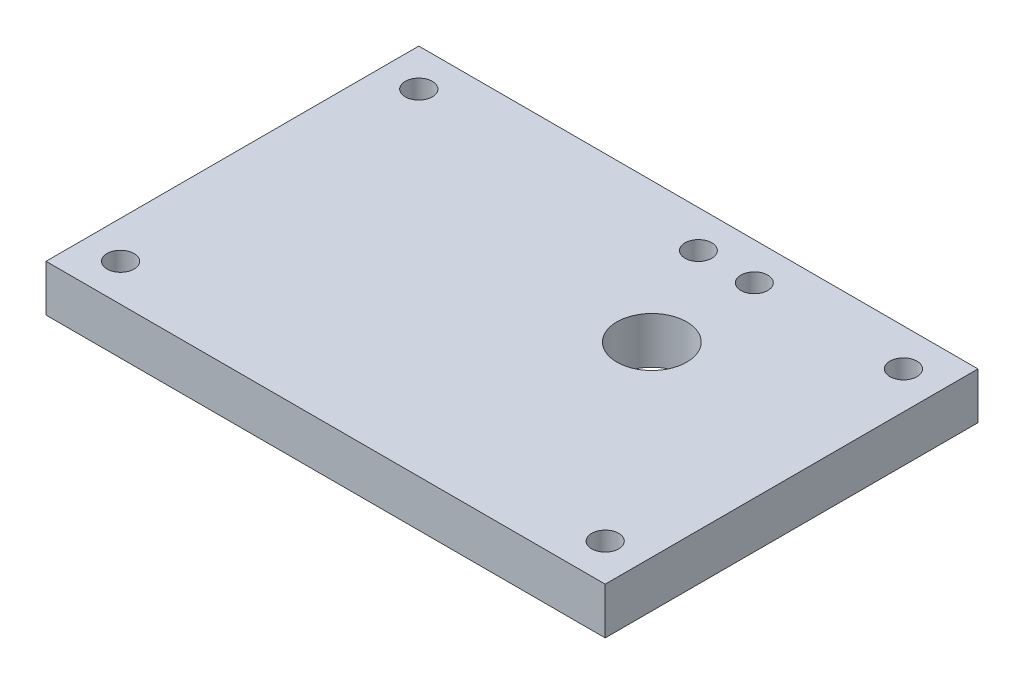
SolidWorks part; units mm, degrees
ref_plane "Front Plane" through (0, 0, 0) normal (0, 0, 1) x (1, 0, 0)
ref_plane "Top Plane" through (0, 0, 0) normal (0, 1, 0) x (1, 0, 0)
ref_plane "Right Plane" through (0, 0, 0) normal (1, 0, 0) x (0, 0, -1)
sketch "Sketch1" plane through (0, 0, 0) normal (0, 1, 0) x (1, 0, 0)
  line L1 (-38.1, 25.4) -> (38.1, 25.4)
  line L2 (-38.1, 25.4) -> (-38.1, -25.4)
  line L3 (-38.1, -25.4) -> (38.1, -25.4)
  line L4 (38.1, 25.4) -> (38.1, -25.4)
  line L5 (-38.1, 25.4) -> (38.1, -25.4) construction
  line L6 (-38.1, -25.4) -> (38.1, 25.4) construction
  point P0 (0, 0)
  dimension "D1" = 50.8
  dimension "D2" = 76.2
extrude "Boss-Extrude1" add sketch "Sketch1" along normal blind 6.35
sketch "Sketch2" plane through (0, 6.35, 0) normal (0, 1, 0) x (1, 0, 0)
  line L0 (-38.1, 25.4) -> (-38.1, -25.4) construction
  line L1 (38.1, 25.4) -> (-38.1, 25.4) construction
  line L2 (-38.1, -25.4) -> (38.1, -25.4) construction
  line L3 (38.1, -25.4) -> (38.1, 25.4) construction
  circle A0 centre (-33.02, 20.32) radius 1.8415
  circle A1 centre (-33.02, -20.32) radius 1.8415
  circle A2 centre (33.02, -20.32) radius 1.8415
  circle A3 centre (33.02, 20.32) radius 1.8415
  dimension "D3" = 3.683
  dimension "D1" = 5.08
  dimension "D2" = 5.08
  dimension "D4" = 5.08
  dimension "D5" = 5.08
extrude "Cut-Extrude1" cut sketch "Sketch2" against normal through all from offset 0
sketch "Sketch3" plane through (0, 6.35, 0) normal (0, 1, 0) x (1, 0, 0)
  line L0 (38.1, 25.4) -> (-38.1, 25.4) construction
  line L1 (38.1, -25.4) -> (38.1, 25.4) construction
  circle A0 centre (12.7, 6.35) radius 4.7625
  circle A1 centre (5.08, 20.32) radius 1.8288
  circle A2 centre (12.7, 20.32) radius 1.8288
  dimension "D4" = 9.525
  dimension "D7" = 3.6576
  dimension "D1" = 5.08
  dimension "D2" = 19.05
  dimension "D3" = 25.4
  dimension "D5" = 7.62
  dimension "D6" = 33.02
extrude "Cut-Extrude2" cut sketch "Sketch3" against normal through all contours A0 | A1 | A2 region at (12.7, 6.35, -6.35)
